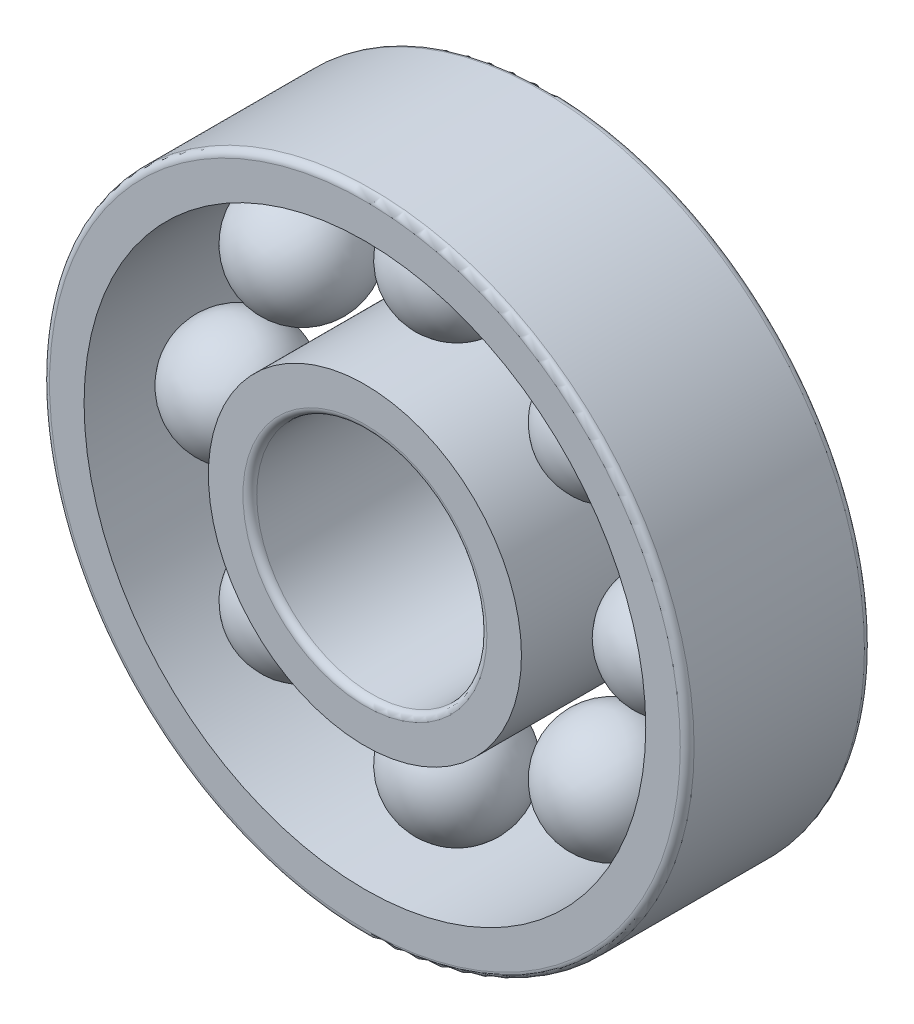
SolidWorks part; units mm, degrees
ref_plane "Front Plane" through (0, 0, 0) normal (0, 0, 1) x (1, 0, 0)
ref_plane "Top Plane" through (0, 0, 0) normal (0, 1, 0) x (1, 0, 0)
ref_plane "Right Plane" through (0, 0, 0) normal (1, 0, 0) x (0, 0, -1)
sketch "S" plane through (0, 0, 0) normal (0, 0, 1) x (1, 0, 0)
  line L0 (-4, 0) -> (4, 0) construction
  circle A0 centre (0, 0) radius 5 construction
  circle A1 centre (0, 0) radius 14 construction
  circle A2 centre (0, 0) radius 6.8 construction
  circle A3 centre (0, 0) radius 12.2 construction
  dimension "ID" = 10
  dimension "OD" = 28
  dimension "IDa" = 13.6
  dimension "ODa" = 24.4
  dimension "B" = 8
ref_axis "Z" through (0, 0, -4.4) along (0, 0, 1)
sketch "InnerS" plane through (0, 0, 0) normal (0, 1, 0) x (1, 0, 0)
  line L0 (5, -4) -> (6.8, -4)
  line L1 (6.8, -4) -> (6.8, 4)
  line L2 (6.8, 4) -> (5, 4)
  line L3 (5, 4) -> (5, -4)
  line L4 (0, -7) -> (0, 7) construction
  dimension "r1" = 5
  dimension "r2" = 6.8
  dimension "z1" = 4
  dimension "z2" = 4
revolve "InnerRing" add sketch "InnerS" angle 360 about L4
sketch "OuterS" plane through (0, 0, 0) normal (0, 1, 0) x (1, 0, 0)
  line L0 (12.2, -4) -> (14, -4)
  line L1 (14, -4) -> (14, 4)
  line L2 (14, 4) -> (12.2, 4)
  line L3 (12.2, 4) -> (12.2, -4)
  line L4 (0, -7) -> (0, 7) construction
  dimension "r1" = 12.2
  dimension "r2" = 14
  dimension "z1" = 4
  dimension "z2" = 4
revolve "OuterRing" add sketch "OuterS" angle 360 about L4
sketch "BallS" plane through (0, 0, 0) normal (0, 1, 0) x (1, 0, 0)
  line L0 (6.935, 0) -> (12.065, 0)
  arc A0 (6.935, 0) -> (12.065, 0) centre (9.5, 0) ccw
  dimension "r" = 2.565
  dimension "p" = 9.5
revolve "Ball" add sketch "BallS" angle 360 about L0
pattern_circular "BallsPattern" count 8 over 360 about axis through (0, 0, -4.4) along (0, 0, 1) of bodies 103
fillet "F1" radius 0.3 2 edges at (14, 0, -4) (14, 0, 4)
fillet "F2" radius 0.3 2 edges at (5, 0, -4) (5, 0, 4)
equation "\"r1@InnerS\" = abs(0.5*\"ID@S\")"
equation "\"r2@InnerS\" = abs(0.5*\"IDa@S\")"
equation "\"z1@InnerS\" = abs(-0.5*\"B@S\")"
equation "\"z2@InnerS\" = abs(0.5*\"B@S\")"
equation "\"r1@OuterS\" = abs(0.5*\"ODa@S\")"
equation "\"r2@OuterS\" = abs(0.5*\"OD@S\")"
equation "\"z1@OuterS\" = abs(-0.5*\"B@S\")"
equation "\"z2@OuterS\" = abs(0.5*\"B@S\")"
equation "\"r@BallS\" = abs(0.2375*\"ODa@S\"-0.2375*\"IDa@S\")"
equation "\"p@BallS\" = abs(0.25*\"IDa@S\"+0.25*\"ODa@S\")"
equation "\"N@BallsPattern\" = int(2.417*(0.25*\"IDa@S\"+0.25*\"ODa@S\")/(0.2375*\"ODa@S\"-0.2375*\"IDa@S\"))"
equation "\"r_min@F2\" = \"r_min@F1\""
